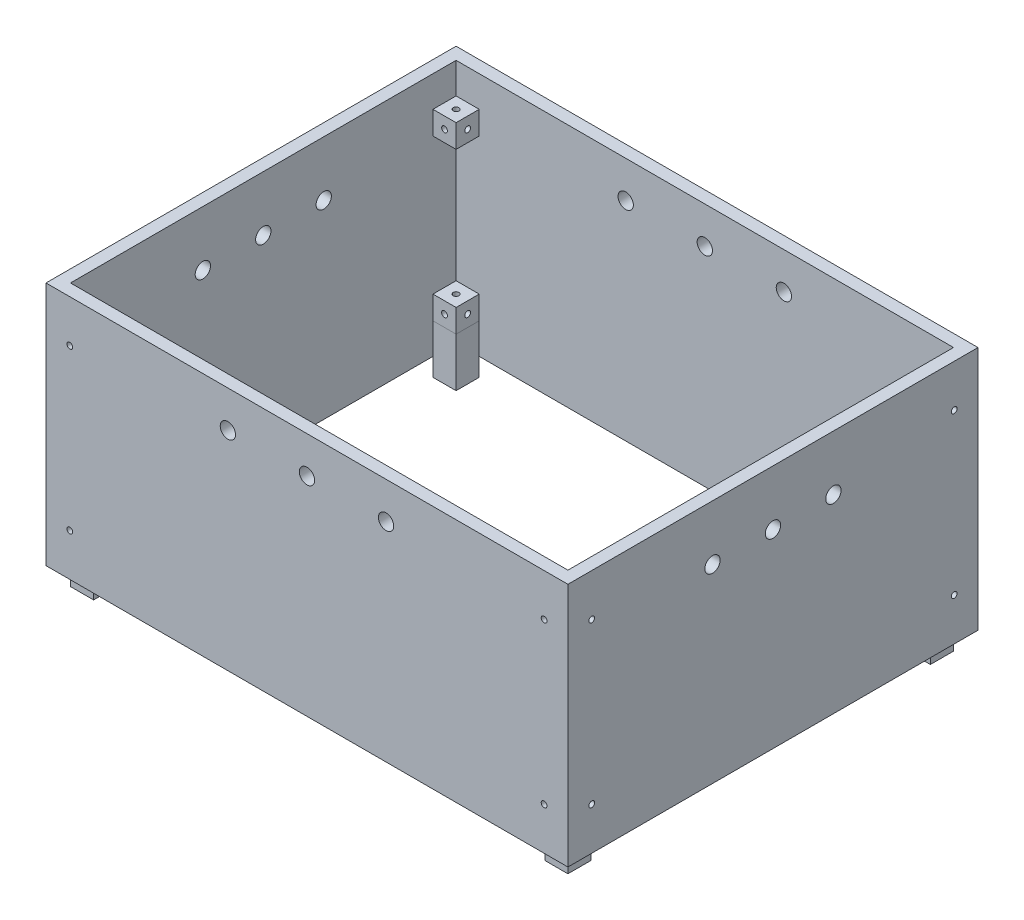
SolidWorks part; units mm, degrees
ref_plane "Front Plane" through (0, 0, 0) normal (0, 0, 1) x (1, 0, 0)
ref_plane "Top Plane" through (0, 0, 0) normal (0, 1, 0) x (1, 0, 0)
ref_plane "Right Plane" through (0, 0, 0) normal (1, 0, 0) x (0, 0, -1)
sketch "Sketch1" plane through (0, 0, 0) normal (0, 1, 0) x (1, 0, 0)
  line L1 (0, 0) -> (270.7, 0)
  line L2 (0, 0) -> (0, 212.7)
  line L3 (0, 212.7) -> (270.7, 212.7)
  line L4 (270.7, 0) -> (270.7, 212.7)
  line L5 (6.35, 6.35) -> (264.35, 6.35)
  line L6 (6.35, 6.35) -> (6.35, 206.35)
  line L7 (6.35, 206.35) -> (264.35, 206.35)
  line L8 (264.35, 6.35) -> (264.35, 206.35)
  dimension "D3" = 6.35
  dimension "D4" = 6.35
  dimension "D5" = 6.35
  dimension "D6" = 6.35
  dimension "D1" = 258
  dimension "D2" = 200
extrude "Walls" add sketch "Sketch1" along normal blind 127
sketch "Sketch2" plane through (0, 0, 0) normal (0, 0, 1) x (1, 0, 0)
  line L0 (0, 127) -> (270.7, 127) construction
  line L1 (135.35, 127) -> (135.35, 107.95) construction
  line L2 (94.33, 127) -> (94.33, 107.95) construction
  line L3 (0, 127) -> (0, 0) construction
  line L4 (176.3667, 127) -> (176.3667, 107.95) construction
  line L5 (270.7, 127) -> (270.7, 0) construction
  circle A0 centre (135.35, 107.95) radius 3.9687
  circle A1 centre (94.33, 107.95) radius 3.9687
  circle A2 centre (176.3667, 107.95) radius 3.9687
  dimension "D2" = 7.9375
  dimension "D4" = 7.9375
  dimension "D7" = 7.9375
  dimension "D1" = 19.05
  dimension "D3" = 94.33
  dimension "D5" = 19.05
  dimension "D6" = 94.3333
  dimension "D8" = 19.05
extrude "RodHolesHeight" cut sketch "Sketch2" against normal through all
sketch "Sketch4" plane through (0, 0, 0) normal (-1, 0, 0) x (0, 0, 1)
  line L0 (-106.35, 127) -> (-106.35, 98.425) construction
  line L1 (-212.7, 127) -> (0, 127) construction
  line L2 (-137.7, 127) -> (-137.7, 98.425) construction
  line L3 (-75, 127) -> (-75, 98.425) construction
  line L4 (-212.7, 127) -> (-212.7, 0) construction
  line L5 (0, 127) -> (0, 0) construction
  circle A0 centre (-106.35, 98.425) radius 3.9687
  circle A1 centre (-137.7, 98.425) radius 3.9687
  circle A2 centre (-75, 98.425) radius 3.9688
  dimension "D2" = 7.9375
  dimension "D5" = 7.9375
  dimension "D6" = 7.9375
  dimension "D1" = 28.575
  dimension "D3" = 75
  dimension "D4" = 75
  dimension "D7" = 28.575
  dimension "D8" = 28.575
extrude "RodHolesWidth" cut sketch "Sketch4" against normal through all contours A1 | A0 | A2
sketch "Sketch3" plane through (0, 0, -6.35) normal (0, 0, -1) x (-1, 0, 0)
  line L14 (-264.35, 111) -> (-252.35, 111)
  line L15 (-264.35, 111) -> (-264.35, 99)
  line L16 (-264.35, 99) -> (-252.35, 99)
  line L17 (-264.35, 0) -> (-6.35, 0)
  line L18 (-6.35, 0) -> (-6.35, 127)
  line L19 (-6.35, 127) -> (-264.35, 127)
  line L20 (-264.35, 127) -> (-264.35, 0)
  line L21 (-264.35, 0) -> (-6.35, 0)
  line L22 (-6.35, 0) -> (-6.35, 127)
  line L23 (-6.35, 127) -> (-264.35, 127)
  line L24 (-264.35, 127) -> (-264.35, 0)
  line L25 (-252.35, 111) -> (-252.35, 99)
  line L26 (-6.35, 111) -> (-18.35, 111)
  line L27 (-6.35, 111) -> (-6.35, 99)
  line L28 (-6.35, 99) -> (-18.35, 99)
  line L29 (-18.35, 111) -> (-18.35, 99)
  line L30 (-264.35, 28) -> (-252.35, 28)
  line L31 (-264.35, 28) -> (-264.35, 16)
  line L32 (-264.35, 16) -> (-252.35, 16)
  line L33 (-252.35, 28) -> (-252.35, 16)
  line L34 (-6.35, 28) -> (-18.35, 28)
  line L35 (-6.35, 28) -> (-6.35, 16)
  line L36 (-6.35, 16) -> (-18.35, 16)
  line L37 (-18.35, 28) -> (-18.35, 16)
  point P20 (-258.35, 16)
  line M35 (-264.35, 127) -> (-264.35, 0)
  dimension "D2" = 12
  dimension "D3" = 16
  dimension "D4" = 16
extrude "ModdingCube" add sketch "Sketch3" along normal blind 12 contours L25 L14 L16 M35 | L33 L30 L24 L32 | L34 L37 L36 L22 | L26 L29 L28 L22 region at (258.35, 105, -6.35) region at (258.35, 22, -6.35) region at (12.35, 105, -6.35) region at (12.35, 22, -6.35)
sketch "Sketch11" plane through (0, 0, -18.35) normal (0, 0, -1) x (-1, 0, 0)
  line L0 (-258.35, 111) -> (-258.35, 105) construction
  line L1 (-264.35, 111) -> (-252.35, 111) construction
  line L2 (-258.35, 105) -> (-252.35, 105) construction
  line L3 (-252.35, 111) -> (-252.35, 99) construction
  line L4 (-12.35, 111) -> (-12.35, 105) construction
  line L5 (-6.35, 111) -> (-18.35, 111) construction
  line L6 (-12.35, 105) -> (-18.35, 105) construction
  line L7 (-18.35, 111) -> (-18.35, 99) construction
  line L8 (-12.35, 28) -> (-12.35, 22) construction
  line L9 (-6.35, 28) -> (-18.35, 28) construction
  line L10 (-12.35, 22) -> (-18.35, 22) construction
  line L11 (-18.35, 28) -> (-18.35, 16) construction
  line L12 (-258.35, 28) -> (-258.35, 22) construction
  line L13 (-264.35, 28) -> (-252.35, 28) construction
  line L14 (-258.35, 22) -> (-252.35, 22) construction
  line L15 (-252.35, 28) -> (-252.35, 16) construction
  line L16 (-252.35, 22) -> (-258.35, 22) construction
  circle A1 centre (-258.35, 105) radius 1.5
  circle A2 centre (-258.35, 22) radius 1.5
  circle A3 centre (-12.35, 105) radius 1.5
  circle A4 centre (-12.35, 22) radius 1.5
  dimension "D1" = 3
extrude "Cut-Extrude1" cut sketch "Sketch11" against normal through all both and the other way through all contours A2 | A1 | A3 | A4
sketch "Sketch17" plane through (0, 28, 0) normal (0, 1, 0) x (1, 0, 0)
  line L0 (12.35, 18.35) -> (12.35, 12.35) construction
  line L1 (6.35, 18.35) -> (18.35, 18.35) construction
  line L2 (12.35, 12.35) -> (18.35, 12.35) construction
  line L3 (18.35, 18.35) -> (18.35, 6.35) construction
  line L4 (258.35, 18.35) -> (258.35, 12.35) construction
  line L5 (264.35, 18.35) -> (252.35, 18.35) construction
  line L6 (258.35, 12.35) -> (252.35, 12.35) construction
  line L7 (252.35, 18.35) -> (252.35, 6.35) construction
  circle A0 centre (12.35, 12.35) radius 1.5
  circle A1 centre (258.35, 12.35) radius 1.5
  dimension "D1" = 3
  dimension "D2" = 3
extrude "Cut-Extrude4" cut sketch "Sketch17" against normal through all both and the other way through all
sketch "Sketch15" plane through (252.35, 0, 0) normal (-1, 0, 0) x (0, 0, 1)
  line L0 (-12.35, 111) -> (-12.35, 105) construction
  line L1 (-18.35, 111) -> (-6.35, 111) construction
  line L2 (-12.35, 105) -> (-18.35, 105) construction
  line L3 (-18.35, 111) -> (-18.35, 99) construction
  line L5 (-12.35, 28) -> (-12.35, 22) construction
  line L6 (-18.35, 28) -> (-6.35, 28) construction
  line L7 (-12.35, 22) -> (-18.35, 22) construction
  line L8 (-18.35, 28) -> (-18.35, 16) construction
  circle A0 centre (-12.35, 105) radius 1.5
  circle A1 centre (-12.35, 22) radius 1.5
  dimension "D1" = 3
  dimension "D2" = 3
extrude "Cut-Extrude2" cut sketch "Sketch15" against normal through all both and the other way through all
ref_plane "Plane2" through (0, 0, -106.35) normal (0, 0, -1) x (-1, 0, 0)
mirror "Mirror6" about plane through (0, 0, -106.35) normal (0, 0, -1) of "Cut-Extrude2", "Cut-Extrude4", "Cut-Extrude1", "ModdingCube"
sketch "Sketch18" plane through (0, 16, 0) normal (0, -1, 0) x (1, 0, 0)
  line L1 (6.35, -6.35) -> (18.35, -6.35)
  line L2 (6.35, -6.35) -> (6.35, -18.35)
  line L3 (6.35, -18.35) -> (18.35, -18.35)
  line L4 (18.35, -6.35) -> (18.35, -18.35)
  line L5 (6.35, -206.35) -> (18.35, -206.35)
  line L6 (6.35, -206.35) -> (6.35, -194.35)
  line L7 (6.35, -194.35) -> (18.35, -194.35)
  line L8 (18.35, -206.35) -> (18.35, -194.35)
  line L9 (264.35, -206.35) -> (252.35, -206.35)
  line L10 (264.35, -206.35) -> (264.35, -194.35)
  line L11 (264.35, -194.35) -> (252.35, -194.35)
  line L12 (252.35, -206.35) -> (252.35, -194.35)
  line L13 (264.35, -6.35) -> (252.35, -6.35)
  line L14 (264.35, -6.35) -> (264.35, -18.35)
  line L15 (264.35, -18.35) -> (252.35, -18.35)
  line L16 (252.35, -6.35) -> (252.35, -18.35)
extrude "Pegs" add sketch "Sketch18" along normal blind 25.4 separate body
equation "\"Length\"= 283mm"
equation "\"Width\"= 225mm"
equation "\"WallThickness\"= 12.5mm"
equation "\"UpperWaterJacketThickness\"= 28mm"
equation "\"SpacerHeight\"= 80.2mm"
equation "\"SpacerCornerWidth\"= 10mm"
equation "\"SpacerCornerHeight\"= 60.16mm"
equation "\"SpacerPegDiameter\"= 10mm"
equation "\"SpacerPegHeight\"= 10mm"
equation "\"TubingShort\"= 110mm"
equation "\"TubingLong\"= 175mm"
equation "\"PlateLength\"= 252mm"
equation "\"PlateWidth\"= 190mm"
equation "\"PlateHoleDiameter\"= 5.9mm"
equation "\"PlateHoleBottom\"= 2mm"
equation "\"PlateHoleSide\"= 1.55mm"
equation "\"PlateHoleSpacing\"= 3.1mm"
equation "\"PlateThickness\"= 1.55mm"
equation "\"ReservoirBottom\"= 12.5mm"
equation "\"ReservoirSupportWidth\"= 12mm"
equation "\"ReservoirSupportHeight\"= 15.1mm"
equation "\"ReservoirSupportPlacementHeight\"= 50mm"
equation "\"ReservoirHoleDiameter\"= 12.7mm"
equation "\"ReservoirHoleRight\"= 25mm"
equation "\"ReservoirHoleTop\"= \"ReservoirSupportPlacementHeight\""
equation "\"ReservoirHeight\"= 90mm"
equation "\"ReservoirPortBottom\"= 4mm"
equation "\"ReservoirPortTop\"= 10mm"
equation "\"ReservoirPortWidth\"= 101mm"
equation "\"D3@Sketch1\"=\"CustomSpacerWallThickness\""
equation "\"D4@Sketch1\"=\"CustomSpacerWallThickness\""
equation "\"CustomSpacerWallThickness\"= 6.35mm"
equation "\"D5@Sketch1\"=\"CustomSpacerWallThickness\""
equation "\"D6@Sketch1\"=\"CustomSpacerWallThickness\""
equation "\"CustomSpacerHeight\"= 5in"
equation "\"D1@Walls\" = \"CustomSpacerHeight\""
equation "\"CustomSpacerRodHoleHeight\"= .75in"
equation "\"CustomSpacerRodHoleDiameter\"= .3125in"
equation "\"D4@Sketch2\"=\"CustomSpacerRodHoleDiameter\""
equation "\"D5@Sketch2\"=\"CustomSpacerRodHoleHeight\""
equation "\"D2@Sketch2\"=\"CustomSpacerRodHoleDiameter\""
equation "\"D6@Sketch2\"=\"Length\"/3"
equation "\"D7@Sketch2\"=\"CustomSpacerRodHoleDiameter\""
equation "\"D8@Sketch2\"=\"CustomSpacerRodHoleHeight\""
equation "\"ScrewBlockSide\"= 12mm"
equation "\"D2@Sketch3\"=\"ScrewBlockSide\""
equation "\"ScrewBlockUpperHeight\"= 16mm"
equation "\"D3@Sketch3\"=\"ScrewBlockUpperHeight\""
equation "\"ScrewBlockLowerHeight\"= 16mm"
equation "\"D4@Sketch3\"=\"ScrewBlockLowerHeight\""
equation "\"D1@ModdingCube\" = \"ScrewBlockSide\""
equation "\"InternalLength\"= \"Length\" - ( 2 * \"WallThickness\" )"
equation "\"D1@Sketch1\"=\"InternalLength\""
equation "\"InternalWidth\"= \"Width\" - ( 2 * \"WallThickness\" )"
equation "\"D2@Sketch1\"=\"InternalWidth\""
equation "\"D1@Sketch4\"=\"CustomSpacerRodHoleHeight\"+\"CustomSpacerRodHoleDiameter\"+0.0625in"
equation "\"D2@Sketch4\"=\"CustomSpacerRodHoleDiameter\""
equation "\"D3@Sketch4\"=\"Width\"/3"
equation "\"D4@Sketch4\"=\"Width\"/3"
equation "\"D5@Sketch4\"=\"CustomSpacerRodHoleDiameter\""
equation "\"D6@Sketch4\"=\"CustomSpacerRodHoleDiameter\""
equation "\"D7@Sketch4\"=\"CustomSpacerRodHoleHeight\"+\"CustomSpacerRodHoleDiameter\"+0.0625in"
equation "\"D8@Sketch4\"=\"CustomSpacerRodHoleHeight\"+\"CustomSpacerRodHoleDiameter\"+0.0625in"
equation "\"CustomSpacerPegHeight\"= 1in"
equation "\"CustomSpacerScrewBore\"=3mm"
equation "\"D1@Sketch11\"=\"CustomSpacerScrewBore\""
equation "\"D1\"= \"ScrewBlockSide\" / 2"
equation "\"D1@Sketch15\"=\"CustomSpacerScrewBore\""
equation "\"D2@Sketch15\"=\"CustomSpacerScrewBore\""
equation "\"D2@Sketch17\"=\"CustomSpacerScrewBore\""
equation "\"D1@Pegs\" = \"CustomSpacerPegHeight\""
equation "\"CustomSpacerScrewDepth\"=10mm"
